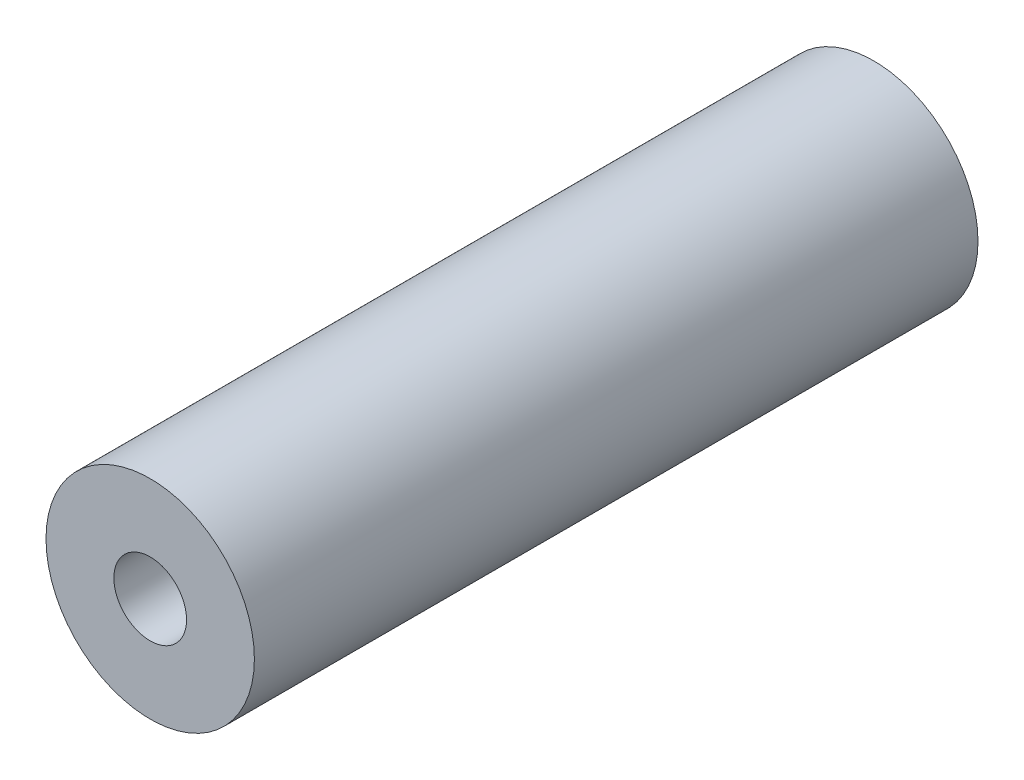
SolidWorks part; units mm, degrees
ref_plane "Front Plane" through (0, 0, 0) normal (0, 0, 1) x (1, 0, 0)
ref_plane "Top Plane" through (0, 0, 0) normal (0, 1, 0) x (1, 0, 0)
ref_plane "Right Plane" through (0, 0, 0) normal (1, 0, 0) x (0, 0, -1)
sketch "Sketch1" plane through (0, 0, 0) normal (0, 0, 1) x (1, 0, 0)
  circle A0 centre (0, 0) radius 2.5527
  circle A1 centre (0, 0) radius 7.3152
  dimension "D1" = 5.1054
  dimension "D2" = 4.7625
extrude "Boss-Extrude1" add sketch "Sketch1" along normal blind 50.8
